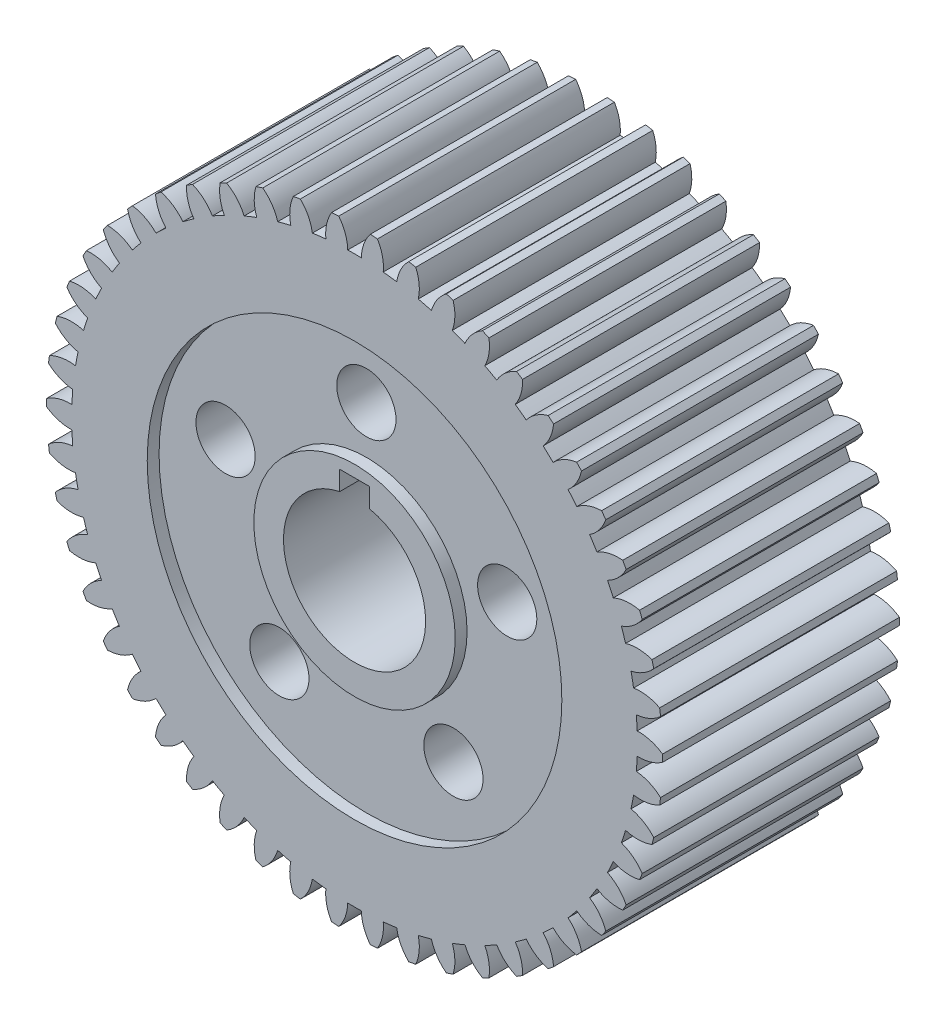
SolidWorks part; units mm, degrees
ref_plane "Front Plane" through (0, 0, 0) normal (0, 0, 1) x (1, 0, 0)
ref_plane "Top Plane" through (0, 0, 0) normal (0, 1, 0) x (1, 0, 0)
ref_plane "Right Plane" through (0, 0, 0) normal (1, 0, 0) x (0, 0, -1)
sketch "Sketch1" plane through (0, 0, 0) normal (0, 0, 1) x (1, 0, 0)
  circle A0 centre (0, 0) radius 47.75
  circle A1 centre (0, 0) radius 50
  circle A2 centre (0, 0) radius 52
  dimension "D1" = 95.5
  dimension "D2" = 100
  dimension "D3" = 104
extrude "Boss-Extrude1" add sketch "Sketch1" along normal mid plane 40 contours A2
sketch "Sketch4" plane through (0, 0, 20) normal (0, 0, 1) x (1, 0, 0)
  line L0 (0, 0) -> (0, 30.6535) construction
  line L1 (0, 0) -> (-1.1479, 47.7362) construction
  line L2 (0, 45.6603) -> (-3.1411, 54.2903) construction
  line L3 (-1.5705, 49.9753) -> (1.5705, 49.9753) construction
  line L4 (0, 0) -> (1.7831, 28.3422) construction
  line L5 (1.5705, 49.9753) -> (4.7054, 49.7781) construction
  arc A0 (-12.8545, 52.84) -> (-1.1479, 47.7362) centre (-8.1876, 47.5669) cw
  circle A1 centre (0, 0) radius 52
  circle A2 centre (0, 0) radius 52
  circle A3 centre (0, 0) radius 50
  circle A4 centre (0, 0) radius 50
  circle A5 centre (0, 0) radius 47.75
  circle A6 centre (0, 0) radius 47.75
  arc A7 (12.8545, 52.84) -> (-12.8545, 52.84) centre (0, 0) ccw
  arc A8 (12.8545, 52.84) -> (1.1479, 47.7362) centre (8.1876, 47.5669) ccw
  circle A9 centre (0, 0) radius 54.3811 construction
  point P25 (-1.5705, 49.9753)
  dimension "D4" = 20
  dimension "D5" = 3.6
extrude "Cut-Extrude1" cut sketch "Sketch4" against normal blind 40 contours A8 A2 A0 A4 | A8 A4 A0 A6 region at (0, 51.0736, 20) region at (0, 48.93, 20)
pattern_circular "CirPattern1" count 50 over 360 about axis through (0, 0, 20) along (0, 0, -1) of "Cut-Extrude1"
sketch "Sketch5" plane through (0, 0, -20) normal (0, 0, -1) x (-1, 0, 0)
  line L2 (-2.5, 11.7367) -> (-2.5, 15)
  line L3 (-2.5, 15) -> (2.5, 15)
  line L4 (2.5, 11.7367) -> (2.5, 15)
  circle A0 centre (0, 0) radius 35
  circle A1 centre (0, 0) radius 17
  arc A2 (-2.5, 11.7367) -> (2.5, 11.7367) centre (0, 0) ccw
  point P5 (0, 12)
  dimension "D1" = 70
  dimension "D2" = 34
  dimension "D3" = 24
  dimension "D4" = 5
  dimension "D5" = 15
extrude "Cut-Extrude2" cut sketch "Sketch5" against normal through all contours L2 A2 L4 L3 region at (0, 0.444, -20)
extrude "Cut-Extrude3" cut sketch "Sketch5<4>" against normal blind 2 contours A0 A1 region at (34.0101, 0, -20)
sketch "Sketch5<4>" plane through (0, 0, -20) normal (0, 0, -1) x (-1, 0, 0) same geometry as "Sketch5"
sketch "Sketch6" plane through (0, 0, 20) normal (0, 0, 1) x (1, 0, 0)
  line L3 (2.5, 11.7367) -> (2.5, 15)
  line L4 (2.5, 15) -> (-2.5, 15)
  line L5 (-2.5, 15) -> (-2.5, 11.7367)
  line L6 (2.5, 11.7367) -> (2.5, 15)
  line L7 (2.5, 15) -> (-2.5, 15)
  line L8 (-2.5, 15) -> (-2.5, 11.7367)
  circle A1 centre (0, 0) radius 17
  circle A2 centre (0, 0) radius 17
  circle A3 centre (0, 0) radius 35
  circle A4 centre (0, 0) radius 35
  arc A5 (-2.5, 11.7367) -> (2.5, 11.7367) centre (0, 0) ccw
  arc A6 (-2.5, 11.7367) -> (2.5, 11.7367) centre (0, 0) ccw
  dimension "D1" = 0
  dimension "D2" = 0
  dimension "D3" = 0
extrude "Cut-Extrude4" cut sketch "Sketch6" against normal blind 2 contours A4 A2 region at (-34.0101, 0, 20)
sketch "Sketch7" plane through (0, 0, 18) normal (0, 0, 1) x (1, 0, 0)
  circle A0 centre (0, 25) radius 5
  circle A5 centre (23.7764, 7.7254) radius 5
  circle A6 centre (14.6946, -20.2254) radius 5
  circle A7 centre (-14.6946, -20.2254) radius 5
  circle A8 centre (-23.7764, 7.7254) radius 5
  point P13 (0, 0)
  dimension "D1" = 10
  dimension "D2" = 25
  dimension "D3" = 5
extrude "Cut-Extrude5" cut sketch "Sketch7" against normal through all
equation "\"m\" = 2'module"
equation "\"n\" = 50'#teeth"
equation "\"Pd\"= \"m\" * \"n\"'Pitch diameter"
equation "\"Od\"= \"Pd\" + 2 * \"m\"'Outer diameter"
equation "\"Id\"= \"Pd\" - 2.25 * \"m\"'Inner diameter"
equation "\"Cp\"= 360 / \"n\"'circular pitch"
equation "\"Gw\"= 40'Gear width"
equation "\"D1@Sketch1\"=\"Id\""
equation "\"D2@Sketch1\"=\"Pd\""
equation "\"D3@Sketch1\"=\"Od\""
equation "\"D1@Boss-Extrude1\"=\"Gw\""
equation "\"phi\"= 20'pressure angle"
equation "\"D4@Sketch4\"=\"phi\""
equation "\"D5@Sketch4\"=\"Cp\"/2"
equation "\"D1@Cut-Extrude1\"=\"Gw\""
equation "\"D1@CirPattern1\"=\"n\""
